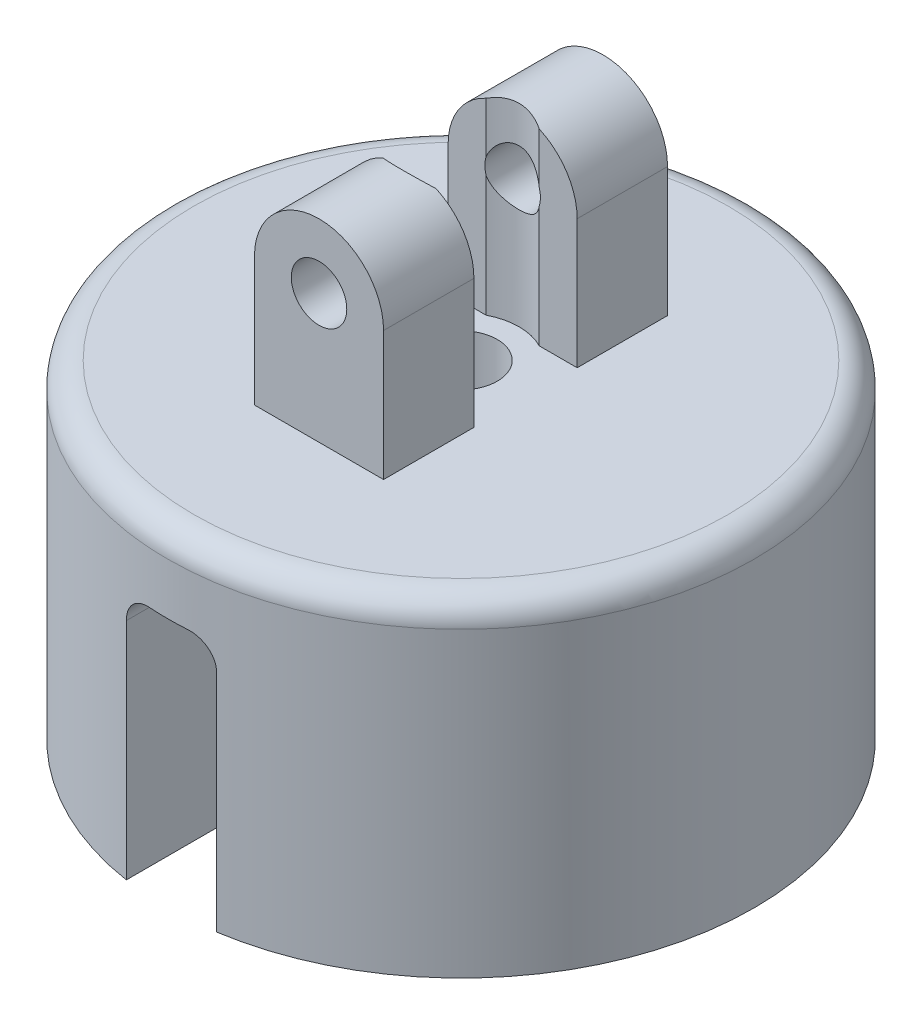
SolidWorks part; units mm, degrees
ref_plane "Plan de face" through (0, 0, 0) normal (0, 0, 1) x (1, 0, 0)
ref_plane "Plan de dessus" through (0, 0, 0) normal (0, 1, 0) x (1, 0, 0)
ref_plane "Plan de droite" through (0, 0, 0) normal (1, 0, 0) x (0, 0, -1)
sketch "Esquisse1" plane through (0, 0, 0) normal (0, 1, 0) x (1, 0, 0)
  line L0 (-55, 0) -> (55, 0) construction
  circle A0 centre (0, 0) radius 12.7
  circle A1 centre (0, 0) radius 22.7
  point P7 (-0.2956, 0)
  dimension "D1" = 25.4
  dimension "D2" = 10
extrude "Boss.-Extru.1" add sketch "Esquisse1" along normal blind 25.4
sketch "Esquisse2" plane through (0, 25.4, 0) normal (0, 1, 0) x (1, 0, 0)
  circle A1 centre (0, 0) radius 22.7
  circle A2 centre (0, 0) radius 22.7
  dimension "D1" = 0
extrude "Boss.-Extru.2" add sketch "Esquisse2" against normal blind 6
sketch "Esquisse3" plane through (0, 0, 0) normal (0, 1, 0) x (1, 0, 0)
  line L1 (-3.5, -12.2082) -> (3.5, -12.2082)
  line L2 (-3.5, -12.2082) -> (-3.5, -22.7)
  line L3 (-3.5, -22.7) -> (3.5, -22.7)
  line L4 (3.5, -12.2082) -> (3.5, -22.7)
  circle A0 centre (0, 0) radius 12.7 construction
  circle A1 centre (0, 0) radius 12.7 construction
  circle A2 centre (0, 0) radius 22.7 construction
  point P6 (0, 0)
  dimension "D1" = 7
extrude "Enlèv. mat.-Extru.1" cut sketch "Esquisse3" along normal up to surface (19.4 mm away) up to face at (0, 19.4, 12.7)
hole_wizard "Dégagement #101" positions "Esquisse5" profile "Esquisse6" hole size "#10" standard "Ansi Inch"
sketch "Esquisse5" plane through (0, 25.4, 0) normal (0, 1, 0) x (1, 0, 0)
  point P0 (0, 0)
sketch "Esquisse6" plane through (0, 25.4, 0) normal (1, 0, 0) x (0, 0, 1)
  line L0 (0, 0) -> (0, 10.6864)
  line L1 (0, 10.6864) -> (2.8067, 9)
  line L2 (2.8067, 9) -> (2.8067, 0)
  line L5 (2.8067, 0) -> (0, 0)
  line L10 (0, 10.6864) -> (-2.8067, 9) construction
  line L11 (0, -6.35) -> (0, 107.95) construction
  dimension "Diamètre du perçage" = 5.6134
  dimension "Profondeur du perçage" = 9
  dimension "Angle de pointe" = 118
fillet "Congé1" radius 2 3 edges at (-3.5, 19.4, 17.3184) (3.5, 19.4, 17.3184) (0, 25.4, 22.7)
chamfer "Chanfrein1" distance 3 angle 15 1 edges at (0, 0, -12.7) first distance on face at (0.0554, 12.3961, 3.9556)
sketch "Esquisse7" plane through (0, 0, 0) normal (0, 0, 1) x (1, 0, 0)
  line L0 (-5, 25.4) -> (-5, 35.4)
  line L1 (20.7, 25.4) -> (-20.7, 25.4) construction
  line L3 (5, 35.4) -> (5, 25.4)
  line L4 (5, 25.4) -> (-5, 25.4)
  line L5 (0, -13.97) -> (0, 13.97) construction
  arc A0 (5, 35.4) -> (-5, 35.4) centre (0, 35.4) ccw
  circle A1 centre (0, 35.4) radius 2.15
  point P7 (0, 25.4)
  dimension "D2" = 5
  dimension "D3" = 4.3
  dimension "D1" = 10
extrude "Boss.-Extru.3" add sketch "Esquisse7" along normal blind 7 from offset 4
mirror "Symétrie1" about plane through (0, 0, 0) normal (0, 0, 1) of "Boss.-Extru.3"
sketch "Esquisse8" plane through (0, 25.4, 0) normal (0, 1, 0) x (1, 0, 0)
  circle A0 centre (0, 0) radius 4.5
  dimension "D1" = 9
extrude "Enlèv. mat.-Extru.2" cut sketch "Esquisse8" along normal through all
